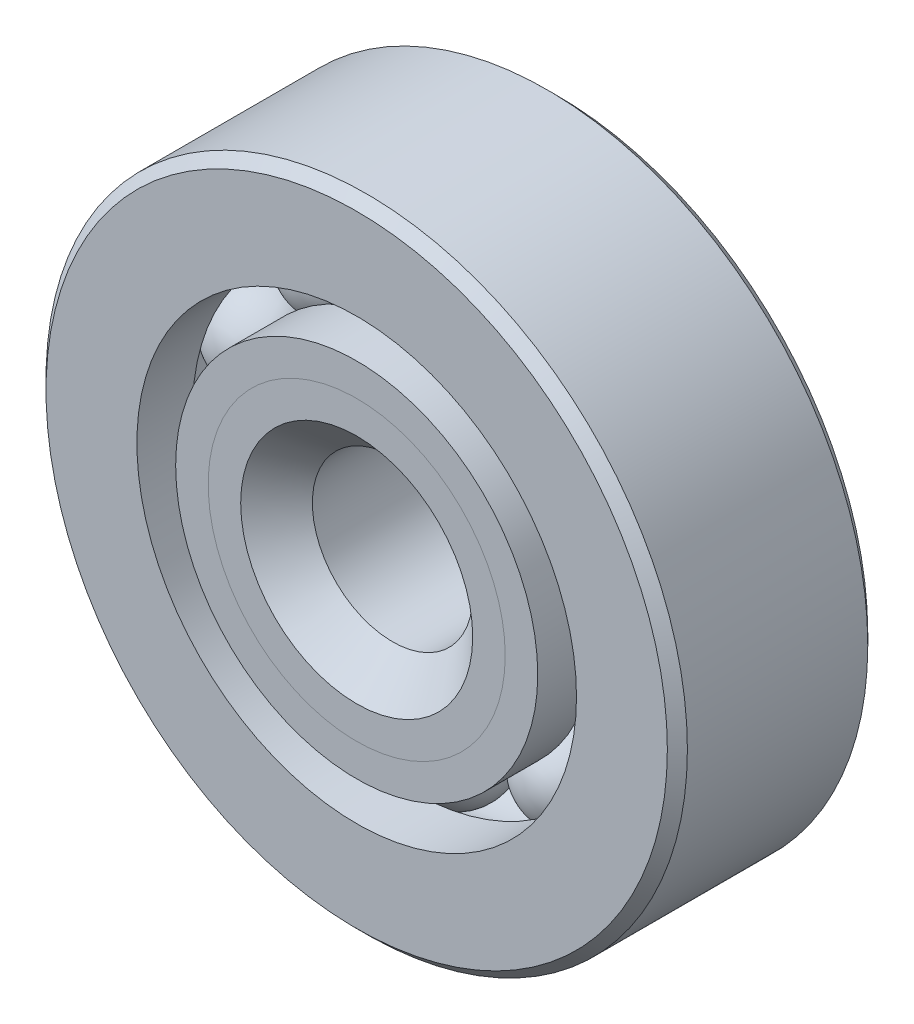
SolidWorks part; units mm, degrees
ref_plane "Front Plane" through (0, 0, 0) normal (0, 0, 1) x (1, 0, 0)
ref_plane "Top Plane" through (0, 0, 0) normal (0, 1, 0) x (1, 0, 0)
ref_plane "Right Plane" through (0, 0, 0) normal (1, 0, 0) x (0, 0, -1)
sketch "Sketch1" plane through (0, 0, 0) normal (1, 0, 0) x (0, 0, -1)
  line L0 (-1.9844, 0) -> (1.9844, 0) construction
  line L1 (0, 6.35) -> (0, -6.35) construction
  line L2 (1.7859, 6.35) -> (-1.7859, 6.35)
  line L3 (-1.7859, 6.35) -> (-1.9844, 6.1516)
  line L4 (-1.9844, 6.1516) -> (-1.9844, 4.3525)
  line L5 (-1.9844, 4.3525) -> (-0.8819, 4.3525)
  line L6 (1.9844, 4.3525) -> (0.8819, 4.3525)
  line L7 (1.9844, 6.1516) -> (1.9844, 4.3525)
  line L8 (1.7859, 6.35) -> (1.9844, 6.1516)
  line L9 (0, 6.35) -> (0, 3.9688) construction
  line L10 (0, 3.9688) -> (0, 1.5875) construction
  arc A0 (-0.8819, 4.3525) -> (0.8819, 4.3525) centre (0, 3.9688) cw
  point P14 (0, 1.5875)
  dimension "Width" = 3.9688
  dimension "OD" = 12.7
  dimension "D1" = 45
  dimension "D2" = 0.1984
  dimension "D3" = 1.7639
  dimension "D4" = 0.3838
revolve "Revolve1" add sketch "Sketch1" angle 360 about L0
sketch "Sketch2" plane through (0, 0, 0) normal (1, 0, 0) x (0, 0, -1)
  line L0 (-1.9844, 3.585) -> (-0.8819, 3.585)
  line L1 (-1.9844, 6.1516) -> (-1.9844, -6.1516) construction
  line L2 (-1.9844, 3.585) -> (-1.9844, 2.9411)
  line L3 (-1.9844, 2.9411) -> (-1.3405, 2.2972)
  line L4 (-1.3405, 2.2972) -> (0, 2.2972)
  line L5 (0, 6.35) -> (0, -6.35) construction
  line L6 (0, 2.2972) -> (0, 3.0069)
  line L7 (0, 3.0069) -> (0, 1.5875) construction
  line L8 (-1.9844, 3.585) -> (-1.9844, 2.2972) construction
  line L9 (-1.9844, 2.2972) -> (-1.3405, 2.2972) construction
  arc A0 (-0.8819, 3.585) -> (0, 3.0069) centre (0, 3.9688) ccw
  arc A1 (0.8819, 4.3525) -> (-0.8819, 4.3525) centre (0, 3.9688) ccw construction
  circle A2 centre (0, 3.9688) radius 0.9618 construction
  dimension "D1" = 45
revolve "Revolve2" add sketch "Sketch2" angle 360 about L0
sketch "Sketch3" plane through (0, 0, 0) normal (1, 0, 0) x (0, 0, -1)
  line L0 (-1.9844, 2.9411) -> (-1.3405, 2.2972)
  line L1 (-1.3405, 2.2972) -> (0, 2.2972)
  line L2 (0, 2.2972) -> (0, 3.0069)
  line L3 (-1.9844, 2.9411) -> (-1.9844, 2.2972)
  line L4 (-1.9844, 3.585) -> (-1.9844, 2.2972) construction
  line L5 (-1.9844, 2.2972) -> (-1.2747, 1.5875)
  line L6 (-1.2747, 1.5875) -> (1.7859, 1.5875)
  line L7 (1.7859, 6.35) -> (1.7859, -6.35) construction
  line L8 (1.7859, 1.5875) -> (1.9844, 1.7859)
  line L9 (1.9844, -6.1516) -> (1.9844, 6.1516) construction
  line L10 (1.9844, 1.7859) -> (1.9844, 3.585)
  line L11 (1.9844, 3.585) -> (0.8819, 3.585)
  line L13 (1.7859, 6.35) -> (1.9844, 6.1516) construction
  circle A0 centre (0, 3.9688) radius 0.9618 construction
  arc A1 (0.8819, 3.585) -> (0, 3.0069) centre (0, 3.9688) cw
revolve "Revolve3" add sketch "Sketch3" angle 360 about L0
sketch "Sketch4" plane through (0, 0, 0) normal (1, 0, 0) x (0, 0, -1)
  line L0 (-0.9618, 3.9688) -> (0.9618, 3.9688)
  circle A1 centre (0, 3.9688) radius 0.9618 construction
  arc A2 (-0.9618, 3.9688) -> (0.9618, 3.9688) centre (0, 3.9688) cw
  arc A3 (0.8819, 4.3525) -> (-0.8819, 4.3525) centre (0, 3.9688) ccw construction
revolve "Revolve4" add sketch "Sketch4" angle 360 about L0
ref_axis "Axis1" through (0, 0, -1.9844) along (0, 0, 1)
pattern_circular "CirPattern1" count 10 every 36 about axis through (0, 0, -1.9844) along (0, 0, 1) of bodies 104
equation "\"D2@Sketch1\" = \"Width@Sketch1\"*.05"
equation "\"D3@Sketch1\" = \"Width@Sketch1\"/2.25"
equation "\"D4@Sketch1\" = (((\"OD@Sketch1\"-\"Width@Sketch1\")/2)/3.25)/3.5"
equation "\"D2@CirPattern1\" = 360/\"Balls@CirPattern1\""
